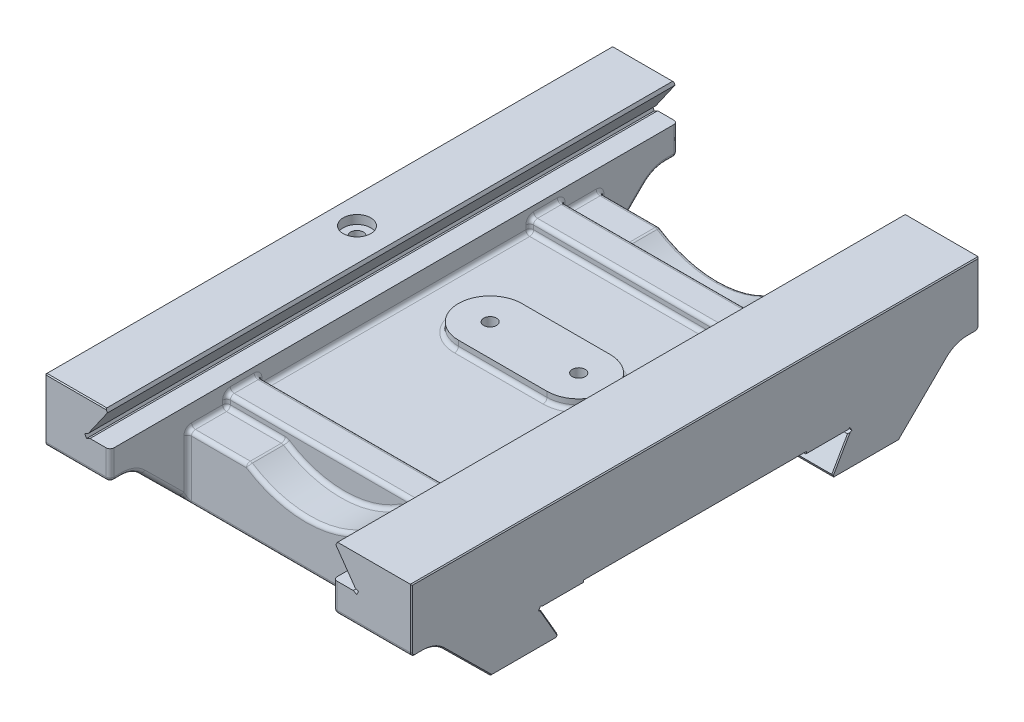
SolidWorks part; units mm, degrees
material "Ductile Iron (SN)"
ref_plane "Front Plane" through (0, 0, 0) normal (0, 0, 1) x (1, 0, 0)
ref_plane "Top Plane" through (0, 0, 0) normal (0, 1, 0) x (1, 0, 0)
ref_plane "Right Plane" through (0, 0, 0) normal (1, 0, 0) x (0, 0, -1)
sketch "Sketch1" plane through (0, 0, 0) normal (1, 0, 0) x (0, 0, -1)
  line L0 (0, 0) -> (0, 200.7195) construction
  line L1 (-185.7375, 77.7875) -> (185.7375, 77.7875)
  line L2 (185.7375, 77.7875) -> (185.7375, 36.5125)
  line L3 (185.7375, 36.5125) -> (178.1175, 36.5125)
  line L4 (164.7261, 31.0114) -> (133.35, 0)
  line L5 (133.35, 0) -> (88.7684, 0)
  line L6 (-133.35, 0) -> (-164.7261, 31.0114)
  line L7 (-178.1175, 36.5125) -> (-185.7375, 36.5125)
  line L8 (-185.7375, 36.5125) -> (-185.7375, 77.7875)
  line L9 (-73.025, 24.13) -> (73.025, 24.13)
  line L10 (73.025, 24.13) -> (73.025, 22.225)
  line L11 (73.025, 22.225) -> (101.6, 22.225)
  line L12 (101.6, 22.225) -> (88.7684, 0)
  line L13 (-73.025, 24.13) -> (-73.025, 22.225)
  line L14 (-73.025, 22.225) -> (-101.6, 22.225)
  line L15 (-101.6, 22.225) -> (-88.7684, 0)
  line L16 (-88.7684, 0) -> (-133.35, 0)
  arc A0 (178.1175, 36.5125) -> (164.7261, 31.0114) centre (178.1175, 17.4625) ccw
  arc A1 (-164.7261, 31.0114) -> (-178.1175, 36.5125) centre (-178.1175, 17.4625) ccw
  point P6 (0, 77.7875)
  point P19 (0, 24.13)
  point P25 (0, 24.13)
  dimension "D6" = 19.05
  dimension "D1" = 266.7
  dimension "D2" = 371.475
  dimension "D3" = 77.7875
  dimension "D4" = 7.62
  dimension "D5" = 41.275
  dimension "D7" = 203.2
  dimension "D8" = 60
  dimension "D9" = 22.225
  dimension "D10" = 146.05
  dimension "D11" = 1.905
extrude "Boss-Extrude1" add sketch "Sketch1" along normal mid plane 239.7125
sketch "Sketch2" plane through (0, 0, 0) normal (0, 0, -1) x (-1, 0, 0)
  line L0 (-69.0563, 77.7875) -> (-84.6184, 55.5625)
  line L1 (-119.8563, 77.7875) -> (119.8563, 77.7875) construction
  line L2 (-84.6184, 55.5625) -> (-68.7434, 55.5625)
  line L3 (-68.7434, 55.5625) -> (-68.7434, 49.5935)
  line L4 (-68.7434, 49.5935) -> (77.3066, 49.5935)
  line L5 (77.3066, 49.5935) -> (77.3066, 55.5625)
  line L6 (77.3066, 55.5625) -> (93.1816, 55.5625)
  line L7 (93.1816, 55.5625) -> (77.6195, 77.7875)
  line L8 (77.6195, 77.7875) -> (-69.0563, 77.7875)
  line L9 (4.2816, 49.5935) -> (4.2816, 77.7875) construction
  dimension "D1" = 22.225
  dimension "D2" = 55
  dimension "D3" = 146.05
  dimension "D4" = 28.194
  dimension "D5" = 177.8
  dimension "D6" = 50.8
extrude "Cut-Extrude1" cut sketch "Sketch2" against normal through all and the other way through all
sketch "Sketch3" plane through (0, 49.5935, 0) normal (0, 1, 0) x (1, 0, 0)
  line L0 (-77.3066, -185.7375) -> (-77.3066, 185.7375) construction
  line L1 (-77.3066, 88.9) -> (68.7434, 88.9)
  line L2 (-77.3066, 88.9) -> (-77.3066, -88.9)
  line L3 (-77.3066, -88.9) -> (68.7434, -88.9)
  line L4 (68.7434, 88.9) -> (68.7434, -88.9)
  line L5 (-77.3066, 88.9) -> (68.7434, -88.9) construction
  line L6 (-77.3066, -88.9) -> (68.7434, 88.9) construction
  line L7 (68.7434, -185.7375) -> (68.7434, 185.7375) construction
  line L9 (-77.3066, 185.7375) -> (68.7434, 185.7375)
  line L10 (-77.3066, 185.7375) -> (-77.3066, 109.5375)
  line L11 (-77.3066, 109.5375) -> (68.7434, 109.5375)
  line L12 (68.7434, 185.7375) -> (68.7434, 109.5375)
  line L13 (-77.3066, 185.7375) -> (68.7434, 109.5375) construction
  line L14 (-77.3066, 109.5375) -> (68.7434, 185.7375) construction
  line L15 (-77.3066, -185.7375) -> (68.7434, -185.7375)
  line L16 (-77.3066, -185.7375) -> (-77.3066, -109.5375)
  line L17 (-77.3066, -109.5375) -> (68.7434, -109.5375)
  line L18 (68.7434, -185.7375) -> (68.7434, -109.5375)
  line L19 (-77.3066, -185.7375) -> (68.7434, -109.5375) construction
  line L20 (-77.3066, -109.5375) -> (68.7434, -185.7375) construction
  point P4 (-4.2816, 0)
  point P14 (-4.2816, 147.6375)
  point P20 (-4.2816, -147.6375)
  dimension "D1" = 177.8
  dimension "D2" = 76.2
  dimension "D3" = 76.2
extrude "Cut-Extrude2" cut sketch "Sketch3" against normal offset from surface (7.747 mm away) 35.941 up to face at (-98.7379, 77.7875, 0)
sketch "Sketch4" plane through (0, 41.8465, 0) normal (0, 1, 0) x (1, 0, 0)
  line L0 (-77.3066, -185.7375) -> (-77.3066, 185.7375) construction
  line L1 (-77.3066, -134.9375) -> (68.7434, -134.9375)
  line L2 (-77.3066, -134.9375) -> (-77.3066, -185.7375)
  line L3 (-77.3066, -185.7375) -> (68.7434, -185.7375)
  line L4 (68.7434, -134.9375) -> (68.7434, -185.7375)
  line L5 (-77.3066, -134.9375) -> (68.7434, -185.7375) construction
  line L6 (-77.3066, -185.7375) -> (68.7434, -134.9375) construction
  line L7 (68.7434, -185.7375) -> (68.7434, 185.7375) construction
  line L8 (-77.3066, 185.7375) -> (68.7434, 185.7375)
  line L9 (-77.3066, 185.7375) -> (-77.3066, 134.9375)
  line L10 (-77.3066, 134.9375) -> (68.7434, 134.9375)
  line L11 (68.7434, 185.7375) -> (68.7434, 134.9375)
  line L12 (-77.3066, 185.7375) -> (68.7434, 134.9375) construction
  line L13 (-77.3066, 134.9375) -> (68.7434, 185.7375) construction
  point P4 (-4.2816, -160.3375)
  point P12 (-4.2816, 160.3375)
  dimension "D1" = 50.8
  dimension "D2" = 50.8
extrude "Cut-Extrude3" cut sketch "Sketch4" against normal through all
sketch "Sketch5" plane through (0, 0, 134.9375) normal (0, 0, 1) x (1, 0, 0)
  line L0 (68.7434, 41.8465) -> (-77.3066, 41.8465) construction
  line L1 (-38.1, 41.8465) -> (38.1, 41.8465)
  arc A0 (-38.1, 41.8465) -> (38.1, 41.8465) centre (0, 99.6315) ccw
  dimension "D2" = 11.43
  dimension "D1" = 76.2
extrude "Cut-Extrude4" cut sketch "Sketch5" against normal blind 25.4 and the other way through all
extrude "Cut-Extrude5" cut sketch "Sketch5<3>" along normal blind 25.4 from surface starting at face at (-4.2816, 21.7078, -134.9375)
sketch "Sketch5<3>" plane through (0, 0, 134.9375) normal (0, 0, 1) x (1, 0, 0) same geometry as "Sketch5"
sketch "Sketch6" plane through (0, 0, 185.7375) normal (0, 0, 1) x (1, 0, 0)
  line L0 (-93.1816, 55.5625) -> (-57.2091, 74.2886) construction
  line L1 (-93.1816, 55.5625) -> (-77.6195, 77.7875) construction
  line L2 (-77.3066, 55.5625) -> (-93.1816, 55.5625) construction
  line L3 (-93.8571, 56.6427) -> (-92.6842, 54.3897)
  line L4 (-93.8571, 56.6427) -> (-91.6041, 57.8155)
  line L5 (-92.6842, 54.3897) -> (-90.4312, 55.5625)
  line L6 (-91.6041, 57.8155) -> (-90.4312, 55.5625)
  line L7 (-93.8571, 56.6427) -> (-90.4312, 55.5625) construction
  line L8 (-92.6842, 54.3897) -> (-91.6041, 57.8155) construction
  line L9 (84.6184, 55.5625) -> (54.0758, 71.462) construction
  line L10 (84.6184, 55.5625) -> (68.7434, 55.5625) construction
  line L11 (69.0563, 77.7875) -> (84.6184, 55.5625) construction
  line L12 (83.0408, 57.8155) -> (81.8679, 55.5625)
  line L13 (83.0408, 57.8155) -> (85.2938, 56.6427)
  line L14 (81.8679, 55.5625) -> (84.121, 54.3897)
  line L15 (85.2938, 56.6427) -> (84.121, 54.3897)
  line L16 (83.0408, 57.8155) -> (84.121, 54.3897) construction
  line L17 (81.8679, 55.5625) -> (85.2938, 56.6427) construction
  point P8 (-92.1441, 56.1026)
  point P20 (83.5809, 56.1026)
  dimension "D1" = 2.54
  dimension "D2" = 2.54
  dimension "D3" = 2.54
  dimension "D4" = 2.54
extrude "Cut-Extrude6" cut sketch "Sketch6" against normal through all
sketch "Sketch8" plane through (119.8563, 0, 0) normal (1, 0, 0) x (0, 0, -1)
  line L0 (-101.6, 22.225) -> (-74.3393, 6.486) construction
  line L1 (-88.7684, 0) -> (-101.6, 22.225) construction
  line L2 (-101.6, 22.225) -> (-73.025, 22.225) construction
  line L3 (-101.2597, 23.495) -> (-102.5297, 21.2953)
  line L4 (-101.2597, 23.495) -> (-99.06, 22.225)
  line L5 (-102.5297, 21.2953) -> (-100.33, 20.0253)
  line L6 (-99.06, 22.225) -> (-100.33, 20.0253)
  line L7 (-101.2597, 23.495) -> (-100.33, 20.0253) construction
  line L8 (-102.5297, 21.2953) -> (-99.06, 22.225) construction
  line L9 (101.6, 22.225) -> (85.9946, 13.2152) construction
  line L10 (73.025, 22.225) -> (101.6, 22.225) construction
  line L11 (101.6, 22.225) -> (88.7684, 0) construction
  line L12 (102.5297, 21.2953) -> (101.2597, 23.495)
  line L13 (102.5297, 21.2953) -> (100.33, 20.0253)
  line L14 (101.2597, 23.495) -> (99.06, 22.225)
  line L15 (100.33, 20.0253) -> (99.06, 22.225)
  line L16 (102.5297, 21.2953) -> (99.06, 22.225) construction
  line L17 (101.2597, 23.495) -> (100.33, 20.0253) construction
  point P8 (-100.7949, 21.7601)
  point P20 (100.7949, 21.7601)
  dimension "D1" = 2.54
  dimension "D2" = 2.54
extrude "Cut-Extrude9" cut sketch "Sketch8" against normal through all
sketch "Sketch7" plane through (0, 24.13, 0) normal (0, -1, 0) x (1, 0, 0)
  line L0 (119.8563, 73.025) -> (-119.8563, 73.025) construction
  line L1 (-103.9812, 73.025) -> (103.9812, 73.025)
  line L2 (-110.3312, 66.675) -> (-110.3312, 41.275)
  line L3 (-103.9812, -73.025) -> (103.9812, -73.025)
  line L4 (110.3312, 66.675) -> (110.3313, -66.675)
  line L5 (-110.3312, 73.025) -> (110.3313, -73.025) construction
  line L6 (-110.3312, -73.025) -> (110.3312, 73.025) construction
  line L7 (119.8563, -73.025) -> (-119.8563, -73.025) construction
  line L8 (-119.8563, 73.025) -> (-119.8563, -73.025) construction
  line L9 (119.8563, 73.025) -> (119.8563, -73.025) construction
  line L10 (-110.3312, -41.275) -> (-110.3312, -66.675)
  line L11 (-103.9812, 34.925) -> (-88.1062, 34.925)
  line L13 (-103.9812, -34.925) -> (-88.1062, -34.925)
  line L14 (-81.7562, 28.575) -> (-81.7562, -28.575)
  line L15 (-110.3312, 34.925) -> (-81.7562, -34.925) construction
  line L16 (-110.3312, -34.925) -> (-81.7562, 34.925) construction
  arc A0 (103.9812, -73.025) -> (110.3313, -66.675) centre (103.9813, -66.675) ccw
  arc A1 (-110.3312, -66.675) -> (-103.9812, -73.025) centre (-103.9812, -66.675) ccw
  arc A2 (-110.3312, -41.275) -> (-103.9812, -34.925) centre (-103.9812, -41.275) cw
  arc A3 (-88.1062, -34.925) -> (-81.7562, -28.575) centre (-88.1062, -28.575) ccw
  arc A4 (-88.1062, 34.925) -> (-81.7562, 28.575) centre (-88.1062, 28.575) cw
  arc A5 (103.9812, 73.025) -> (110.3312, 66.675) centre (103.9813, 66.675) cw
  arc A6 (-103.9812, 73.025) -> (-110.3312, 66.675) centre (-103.9813, 66.675) ccw
  arc A7 (-103.9812, 34.925) -> (-110.3312, 41.275) centre (-103.9813, 41.275) cw
  point P4 (0, 0)
  point P17 (-96.0438, 0)
  point P42 (-119.8563, 0)
  dimension "D5" = 6.35
  dimension "D1" = 9.525
  dimension "D2" = 9.525
  dimension "D3" = 69.85
  dimension "D4" = 38.1
extrude "Cut-Extrude8" cut sketch "Sketch7" against normal blind 6.35
sketch "Sketch9" plane through (0, 41.8465, 0) normal (0, 1, 0) x (1, 0, 0)
  line L0 (-33.3819, 19.0627) -> (24.6062, 19.0627) construction
  line L1 (-33.3819, 39.8272) -> (24.6062, 39.8272)
  line L2 (-33.3819, -1.7018) -> (24.6062, -1.7018)
  line L3 (119.8563, 185.7375) -> (119.8563, -185.7375) construction
  line L4 (119.8563, 185.7375) -> (69.0563, 185.7375) construction
  arc A0 (-33.3819, 39.8272) -> (-33.3819, -1.7018) centre (-33.3819, 19.0627) ccw
  arc A1 (24.6062, -1.7018) -> (24.6062, 39.8272) centre (24.6062, 19.0627) ccw
  point P2 (-4.3878, 19.0627)
  dimension "D3" = 153.2382
  dimension "D4" = 95.25
  dimension "D1" = 41.529
  dimension "D2" = 166.6748
extrude "Boss-Extrude2" add sketch "Sketch9" along normal offset from surface (5.969 mm away) 29.972 up to face at (-98.7379, 77.7875, 0)
sketch "Sketch11" plane through (0, 30.48, 0) normal (0, 1, 0) x (1, 0, 0)
  circle A0 centre (-33.3819, 19.0627) radius 20.7645
  circle A1 centre (24.6062, 19.0627) radius 20.7645
extrude "Boss-Extrude3" add sketch "Sketch11" against normal up to surface (6.35 mm away) up to face at (-102.8084, 24.13, 0)
hole_wizard "CBORE for M8 Hex Head Bolt1" positions "Sketch13" profile "Sketch12" counterbore size "M8" standard "ANSI Metric" end condition through all
sketch "Sketch13" plane through (0, 24.13, 0) normal (0, -1, 0) x (-1, 0, 0)
  point P0 (-24.6062, 19.0627)
  point P3 (33.3819, 19.0627)
sketch "Sketch12" plane through (24.6062, 24.13, -19.0627) normal (1, 0, 0) x (0, 0, -1)
  line L0 (0, 0) -> (0, 53.6575)
  line L1 (0, 53.6575) -> (4.2, 53.6575)
  line L3 (4.2, 53.6575) -> (4.2, 11)
  line L4 (4.2, 11) -> (7.5, 11)
  line L5 (7.5, 11) -> (7.5, 0)
  line L7 (7.5, 0) -> (0, 0)
  line L11 (0, -6.35) -> (0, 107.95) construction
  dimension "Thru Hole Dia." = 8.4
  dimension "Thru Hole Depth" = 53.6575
  dimension "C'Bore Dia." = 15
  dimension "C'Bore Depth" = 11
chamfer "Chamfer1" distance 2.54 angle 60 4 edges at (69.0563, 77.7875, 0) (-77.6195, 77.7875, 0) (0, 0, -88.7684) (0, 0, 88.7684) first distance on face at (94.4562, 77.7875, 0) first distance on face at (-84.6118, 67.8015, 0) first distance on face at (0, 10.0126, -94.5492) first distance on face at (0, 0, 111.0592)
fillet "Fillet1" radius 2.54 88 edges at (68.7434, 45.72, -88.9) (-77.3066, 45.72, -88.9) (-77.3066, 45.72, -109.5375) (68.7434, 45.72, -109.5375) (-77.3066, 45.72, 88.9) (68.7434, 45.72, 88.9) (68.7434, 45.72, 109.5375) (-77.3066, 45.72, 109.5375) (-4.2816, 49.5935, -88.9) (-77.3066, 49.5935, -99.2187) (-4.2816, 49.5935, -109.5375) (68.7434, 49.5935, -99.2188) (-4.2816, 49.5935, 88.9) (68.7434, 49.5935, 99.2188) (-4.2816, 49.5935, 109.5375) (-77.3066, 49.5935, 99.2188) (-4.2816, 41.8465, -88.9) (68.7434, 41.8465, 0) (-4.2816, 41.8465, 88.9) (-77.3066, 41.8465, 0) (53.4217, 41.8465, 134.9375) (0, 30.4165, 134.9375) (-57.7033, 41.8465, 134.9375) (-57.7033, 41.8465, -134.9375) (53.4217, 41.8465, -134.9375) (0, 30.4165, -134.9375) (38.1, 41.8465, -122.2375) (-38.1, 41.8465, -122.2375) (-77.3066, 41.8465, -122.2375) (-77.3066, 21.7078, -134.9375) (68.7434, 21.7078, -134.9375) (68.7434, 41.8465, -122.2375) (-57.7033, 41.8465, -109.5375) (53.4217, 41.8465, -109.5375) (0, 30.4165, -109.5375) (-38.1, 41.8465, 122.2375) (38.1, 41.8465, 122.2375) (68.7434, 21.7078, 134.9375) (68.7434, 41.8465, 122.2375) (53.4217, 41.8465, 109.5375) (-77.3066, 21.7078, 134.9375) (-77.3066, 41.8465, 122.2375) (-57.7033, 41.8465, 109.5375) (0, 30.4165, 109.5375) (-77.3066, 36.5125, -181.9275) (68.7434, 36.5125, 181.9275) (-77.3066, 35.0836, -170.8789) (68.7434, 35.0836, 170.8789) (-77.3066, 16.2902, -149.8318) (68.7434, 16.2902, 149.8318) (-4.2816, 1.569, -134.9375) (-4.2816, 1.569, 134.9375) (68.7434, 36.5125, -181.9275) (68.7434, 35.0836, -170.8789) (-77.3066, 36.5125, 181.9275) (-77.3066, 35.0836, 170.8789) (68.7434, 16.2902, -149.8318) (-77.3066, 16.2902, 149.8318) (0, 30.48, -73.025) (-108.4714, 30.48, -71.1651) (-110.3312, 30.48, -53.975) (-108.4714, 30.48, -36.7849) (-96.0437, 30.48, -34.925) (-83.6161, 30.48, -33.0651) (-81.7562, 30.48, 0) (-83.6161, 30.48, 33.0651) (-96.0437, 30.48, 34.925) (-108.4714, 30.48, 36.7849) (-110.3312, 30.48, 53.975) (-108.4714, 30.48, 71.1651) (0, 30.48, 73.025) (108.4714, 30.48, 71.1651) (110.3312, 30.48, 0) (108.4714, 30.48, -71.1651) (-98.5814, 36.5125, -185.7375) (-77.3066, 46.0375, -185.7375) (68.7434, 46.0375, -185.7375) (94.2998, 36.5125, -185.7375) (94.2998, 36.5125, 185.7375) (68.7434, 46.0375, 185.7375) (-77.3066, 46.0375, 185.7375) (-98.5814, 36.5125, 185.7375) (45.3707, 41.8465, -19.0627) (-4.3878, 41.8465, -39.8272) (-54.1464, 41.8465, -19.0627) (-4.3878, 41.8465, 1.7018) (-33.3819, 30.48, -39.8272) (24.6062, 30.48, -39.8272)
chamfer "Chamfer2" distance 0.635 angle 45 36 edges at (-119.8563, 0, 112.3292) (-119.8563, 22.225, 86.0425) (-119.8563, 11.1125, 95.1842) (-119.8563, 0, -112.3292) (-119.8563, 22.225, -86.0425) (-119.8563, 11.1125, -95.1842) (-119.8563, 15.5057, -149.038) (-119.8563, 15.5057, 149.038) (-119.8563, 35.0836, -170.8789) (-119.8563, 35.0836, 170.8789) (-119.8563, 36.5125, -180.6575) (-119.8563, 36.5125, 180.6575) (-119.8563, 37.2564, -184.9936) (-119.8563, 37.2564, 184.9936) (-119.8563, 58.42, -185.7375) (-119.8563, 58.42, 185.7375) (-99.9514, 77.7875, 185.7375) (-119.8563, 77.7875, 0) (119.8563, 22.225, 86.0425) (119.8563, 11.1125, 95.1842) (119.8563, 0, 112.3292) (119.8563, 22.225, -86.0425) (119.8563, 11.1125, -95.1842) (119.8563, 0, -112.3292) (119.8563, 15.5057, 149.038) (119.8563, 15.5057, -149.038) (119.8563, 35.0836, 170.8789) (119.8563, 35.0836, -170.8789) (119.8563, 36.5125, 180.6575) (119.8563, 36.5125, -180.6575) (119.8563, 37.2564, 184.9936) (119.8563, 37.2564, -184.9936) (119.8563, 58.42, 185.7375) (119.8563, 58.42, -185.7375) (119.8563, 77.7875, 0) (-99.9514, 77.7875, -185.7375)
hole_wizard "CBORE for M8 Hex Head Bolt2" positions "Sketch15" profile "Sketch14" counterbore size "M8" standard "ANSI Metric" end condition through all
sketch "Sketch15" plane through (0, 77.7875, 0) normal (0, 1, 0) x (1, 0, 0)
  line L0 (-119.8563, -185.1025) -> (-119.8563, 185.1025) construction
  point P0 (-101.4412, 0)
  dimension "D1" = 18.415
sketch "Sketch14" plane through (-101.4412, 77.7875, 0) normal (1, 0, 0) x (0, 0, 1)
  line L0 (0, 0) -> (0, 77.7875)
  line L1 (0, 77.7875) -> (4.2, 77.7875)
  line L3 (4.2, 77.7875) -> (4.2, 5.68)
  line L4 (4.2, 5.68) -> (9.005, 5.68)
  line L5 (9.005, 5.68) -> (9.005, 0)
  line L7 (9.005, 0) -> (0, 0)
  line L11 (0, -6.35) -> (0, 107.95) construction
  dimension "Thru Hole Dia." = 8.4
  dimension "Thru Hole Depth" = 77.7875
  dimension "C'Bore Dia." = 18.01
  dimension "C'Bore Depth" = 5.68
sketch "Sketch16" plane through (0, 24.13, 0) normal (0, -1, 0) x (1, 0, 0)
  circle A0 centre (-101.4412, 0) radius 10.0965
  dimension "D1" = 20.193
extrude "Cut-Extrude11" cut sketch "Sketch16" against normal blind 12.065
